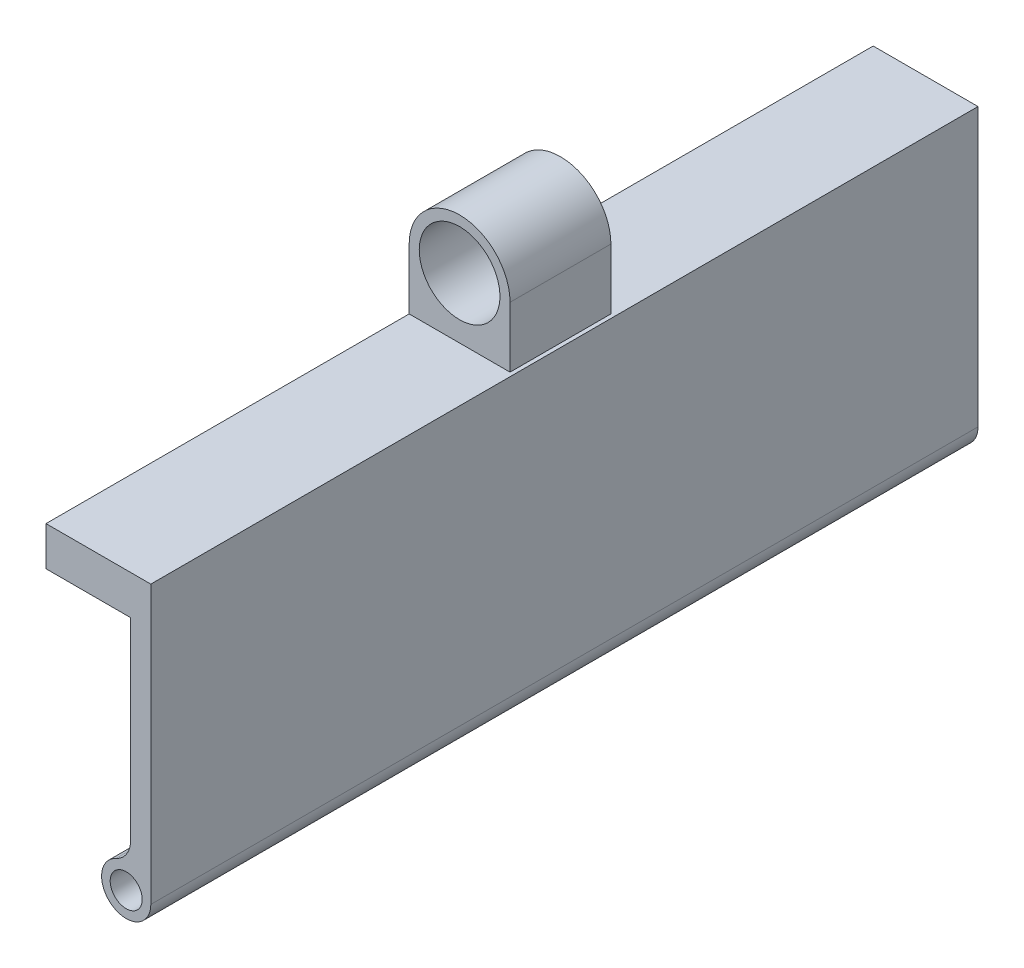
SolidWorks part; units mm, degrees
ref_plane "Front Plane" through (0, 0, 0) normal (0, 0, 1) x (1, 0, 0)
ref_plane "Top Plane" through (0, 0, 0) normal (0, 1, 0) x (1, 0, 0)
ref_plane "Right Plane" through (0, 0, 0) normal (1, 0, 0) x (0, 0, -1)
sketch "Sketch1" plane through (0, 0, 0) normal (0, 0, 1) x (1, 0, 0)
  line L0 (0, 0) -> (3.1723, 0) construction
  line L1 (2.44, 0) -> (2.44, 25)
  line L2 (0.44, 4.49) -> (0.44, 25)
  line L3 (0.44, 25) -> (2.44, 25)
  circle A0 centre (0, 0) radius 1.5875
  arc A1 (-1.0175, 2.2177) -> (2.44, 0) centre (0, 0) ccw
  arc A2 (0.44, 4.49) -> (-1.0175, 2.2177) centre (-2.06, 4.49) cw
  dimension "D1" = 3.175
  dimension "D2" = 4.88
  dimension "D5" = 2.5
  dimension "D3" = 25
  dimension "D4" = 2
extrude "Boss-Extrude1" add sketch "Sketch1" along normal blind 82
sketch "Sketch3" plane through (0, 25, 0) normal (0, 1, 0) x (1, 0, 0)
  line L1 (0.44, -82) -> (2.44, -82)
  line L2 (0.44, -82) -> (0.44, 0)
  line L3 (0.44, 0) -> (2.44, 0)
  line L4 (2.44, -82) -> (2.44, 0)
extrude "Boss-Extrude4" add sketch "Sketch3" along normal blind 2.5
sketch "Sketch6" plane through (0.44, 0, 0) normal (-1, 0, 0) x (0, 0, 1)
  line L1 (82, 27.5) -> (0, 27.5)
  line L2 (82, 27.5) -> (82, 23.6193)
  line L3 (82, 23.6193) -> (0, 23.6193)
  line L4 (0, 27.5) -> (0, 23.6193)
  dimension "D1" = 23.01
extrude "Boss-Extrude5" add sketch "Sketch6" along normal blind 8.39
ref_plane "Plane2" through (-7.95, 23.6193, 0) normal (0, 0, 1) x (1, 0, 0)
ref_plane "Plane3" through (-7.95, 23.6193, 82) normal (0, 0, 1) x (1, 0, 0)
ref_plane "Plane4" through (0.44, 23.6193, 82) normal (0, 0, 1) x (1, 0, 0)
sketch "Sketch8" plane through (0, 0, 0) normal (0, 0, -1) x (-1, 0, 0)
  line L0 (7.95, 27.5) -> (7.95, 33.5)
  line L1 (-2.05, 33.5) -> (-2.05, 27.5)
  line L2 (-2.44, 27.5) -> (7.95, 27.5) construction
  line L3 (7.95, 27.5) -> (-2.05, 27.5)
  circle A0 centre (2.95, 33.5) radius 4
  arc A1 (7.95, 33.5) -> (-2.05, 33.5) centre (2.95, 33.5) ccw
extrude "Boss-Extrude6" add sketch "Sketch8" against normal blind 10 from offset 36 offset against normal yes
sketch "Sketch10" plane through (0.44, 0, 0) normal (-1, 0, 0) x (0, 0, 1)
  line L1 (11.7203, 4.49) -> (23.4406, 4.49)
  line L2 (11.7203, 4.49) -> (11.7203, -2.44)
  line L3 (11.7203, -2.44) -> (23.4406, -2.44)
  line L4 (23.4406, 4.49) -> (23.4406, -2.44)
  line L5 (0, -2.44) -> (82, -2.44) construction
  line L6 (82, 4.49) -> (0, 4.49) construction
  point P4 (0, 4.49)
  point P5 (0, 0)
  point P9 (0, 4.49)
  point P10 (5.7299, 4.49)
  dimension "D1" = 11.7203
  dimension "D2" = 11.7203
extrude "Cut-Extrude1" cut sketch "Sketch10" along normal blind 10
pattern_linear "LPattern1" count 3 spacing 23.4406 along (0, 0, 1) of "Cut-Extrude1"
